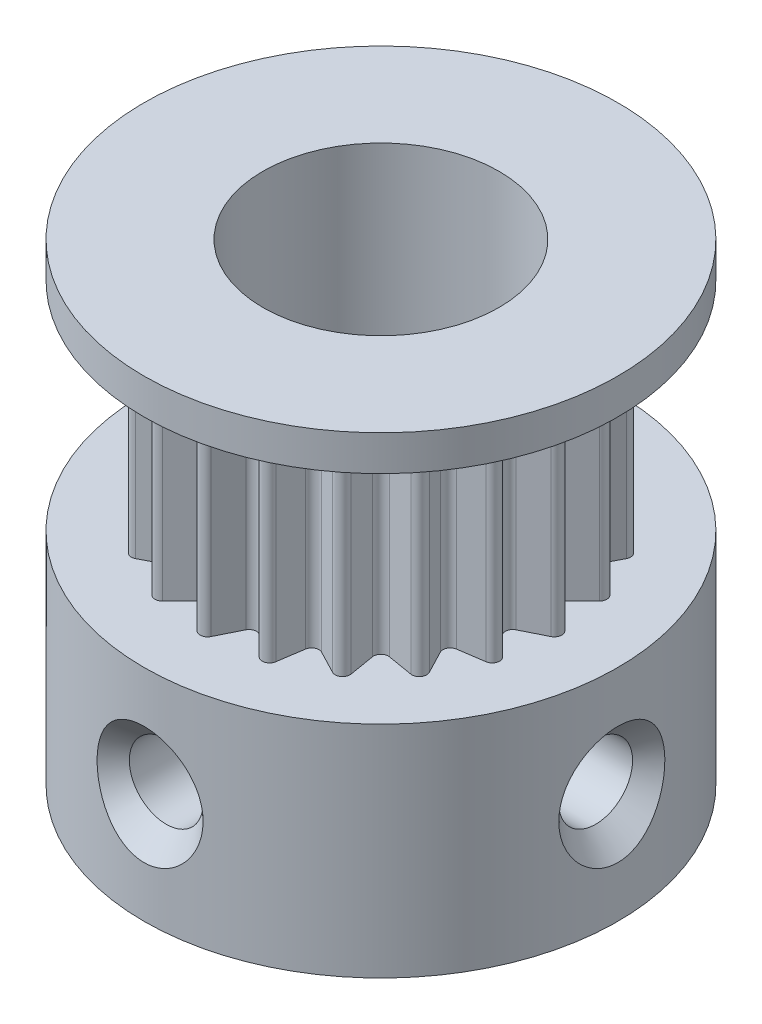
SolidWorks part; units mm, degrees
ref_plane "Front Plane" through (0, 0, 0) normal (0, 0, 1) x (1, 0, 0)
ref_plane "Top Plane" through (0, 0, 0) normal (0, 1, 0) x (1, 0, 0)
ref_plane "Right Plane" through (0, 0, 0) normal (1, 0, 0) x (0, 0, -1)
sketch "Sketch1" plane through (0, 0, 0) normal (0, 1, 0) x (1, 0, 0)
  circle A0 centre (0, 0) radius 8.025
  dimension "D1" = 16.05
extrude "Boss-Extrude1" add sketch "Sketch1" along normal blind 16
sketch "Sketch2" plane through (0, 16, 0) normal (0, 1, 0) x (1, 0, 0)
  line L0 (0.2238, 5.9865) -> (0.6171, 5.1973)
  line L1 (1.0192, 5.1336) -> (1.6371, 5.7627)
  line L2 (0, 0) -> (0, 6.125) construction
  line L3 (0.8408, 5.3088) -> (0.9582, 6.0496) construction
  line L4 (1.8927, 5.8252) -> (0, 0) construction
  line L5 (2.0627, 5.6244) -> (2.1929, 4.7522)
  line L6 (2.5557, 4.5674) -> (3.3378, 4.9747)
  line L7 (3.6998, 4.7117) -> (3.5541, 3.842)
  line L8 (3.842, 3.5541) -> (4.7117, 3.6998)
  line L9 (4.9747, 3.3378) -> (4.5674, 2.5557)
  line L10 (4.7522, 2.1929) -> (5.6244, 2.0627)
  line L11 (5.7627, 1.6371) -> (5.1336, 1.0192)
  line L12 (5.1973, 0.6171) -> (5.9865, 0.2238)
  line L13 (5.9865, -0.2238) -> (5.1973, -0.6171)
  line L14 (5.1336, -1.0192) -> (5.7627, -1.6371)
  line L15 (5.6244, -2.0627) -> (4.7522, -2.1929)
  line L16 (4.5674, -2.5557) -> (4.9747, -3.3378)
  line L17 (4.7117, -3.6998) -> (3.842, -3.5541)
  line L18 (3.5541, -3.842) -> (3.6998, -4.7117)
  line L19 (3.3378, -4.9747) -> (2.5557, -4.5674)
  line L20 (2.1929, -4.7522) -> (2.0627, -5.6244)
  line L21 (1.6371, -5.7627) -> (1.0192, -5.1336)
  line L22 (0.6171, -5.1973) -> (0.2238, -5.9865)
  line L23 (-0.2238, -5.9865) -> (-0.6171, -5.1973)
  line L24 (-1.0192, -5.1336) -> (-1.6371, -5.7627)
  line L25 (-2.0627, -5.6244) -> (-2.1929, -4.7522)
  line L26 (-2.5557, -4.5674) -> (-3.3378, -4.9747)
  line L27 (-3.6998, -4.7117) -> (-3.5541, -3.842)
  line L28 (-3.842, -3.5541) -> (-4.7117, -3.6998)
  line L29 (-4.9747, -3.3378) -> (-4.5674, -2.5557)
  line L30 (-4.7522, -2.1929) -> (-5.6244, -2.0627)
  line L31 (-5.7627, -1.6371) -> (-5.1336, -1.0192)
  line L32 (-5.1973, -0.6171) -> (-5.9865, -0.2238)
  line L33 (-5.9865, 0.2238) -> (-5.1973, 0.6171)
  line L34 (-5.1336, 1.0192) -> (-5.7627, 1.6371)
  line L35 (-5.6244, 2.0627) -> (-4.7522, 2.1929)
  line L36 (-4.5674, 2.5557) -> (-4.9747, 3.3378)
  line L37 (-4.7117, 3.6998) -> (-3.842, 3.5541)
  line L38 (-3.5541, 3.842) -> (-3.6998, 4.7117)
  line L39 (-3.3378, 4.9747) -> (-2.5557, 4.5674)
  line L40 (-2.1929, 4.7522) -> (-2.0627, 5.6244)
  line L41 (-1.6371, 5.7627) -> (-1.0192, 5.1336)
  line L42 (-0.6171, 5.1973) -> (-0.2238, 5.9865)
  line L43 (0, 0) -> (1.0192, 5.1336) construction
  line L44 (0, 0) -> (2.5557, 4.5674) construction
  circle A0 centre (0, 0) radius 6.125 construction
  arc A1 (0.2238, 5.9865) -> (0, 6.125) centre (0, 5.875) ccw
  arc A3 (0.6171, 5.1973) -> (1.0192, 5.1336) centre (0.8408, 5.3088) ccw
  arc A4 (1.6371, 5.7627) -> (1.8927, 5.8252) centre (1.8155, 5.5875) cw
  arc A5 (2.0627, 5.6244) -> (1.8927, 5.8252) centre (1.8155, 5.5875) ccw
  arc A6 (2.1929, 4.7522) -> (2.5557, 4.5674) centre (2.4402, 4.7892) ccw
  arc A7 (3.3378, 4.9747) -> (3.6002, 4.9552) centre (3.4532, 4.753) cw
  arc A8 (3.6998, 4.7117) -> (3.6002, 4.9552) centre (3.4532, 4.753) ccw
  arc A9 (3.5541, 3.842) -> (3.842, 3.5541) centre (3.8007, 3.8007) ccw
  arc A10 (4.7117, 3.6998) -> (4.9552, 3.6002) centre (4.753, 3.4532) cw
  arc A11 (4.9747, 3.3378) -> (4.9552, 3.6002) centre (4.753, 3.4532) ccw
  arc A12 (4.5674, 2.5557) -> (4.7522, 2.1929) centre (4.7892, 2.4402) ccw
  arc A13 (5.6244, 2.0627) -> (5.8252, 1.8927) centre (5.5875, 1.8155) cw
  arc A14 (5.7627, 1.6371) -> (5.8252, 1.8927) centre (5.5875, 1.8155) ccw
  arc A15 (5.1336, 1.0192) -> (5.1973, 0.6171) centre (5.3088, 0.8408) ccw
  arc A16 (5.9865, 0.2238) -> (6.125, 0) centre (5.875, 0) cw
  arc A17 (5.9865, -0.2238) -> (6.125, 0) centre (5.875, 0) ccw
  arc A18 (5.1973, -0.6171) -> (5.1336, -1.0192) centre (5.3088, -0.8408) ccw
  arc A19 (5.7627, -1.6371) -> (5.8252, -1.8927) centre (5.5875, -1.8155) cw
  arc A20 (5.6244, -2.0627) -> (5.8252, -1.8927) centre (5.5875, -1.8155) ccw
  arc A21 (4.7522, -2.1929) -> (4.5674, -2.5557) centre (4.7892, -2.4402) ccw
  arc A22 (4.9747, -3.3378) -> (4.9552, -3.6002) centre (4.753, -3.4532) cw
  arc A23 (4.7117, -3.6998) -> (4.9552, -3.6002) centre (4.753, -3.4532) ccw
  arc A24 (3.842, -3.5541) -> (3.5541, -3.842) centre (3.8007, -3.8007) ccw
  arc A25 (3.6998, -4.7117) -> (3.6002, -4.9552) centre (3.4532, -4.753) cw
  arc A26 (3.3378, -4.9747) -> (3.6002, -4.9552) centre (3.4532, -4.753) ccw
  arc A27 (2.5557, -4.5674) -> (2.1929, -4.7522) centre (2.4402, -4.7892) ccw
  arc A28 (2.0627, -5.6244) -> (1.8927, -5.8252) centre (1.8155, -5.5875) cw
  arc A29 (1.6371, -5.7627) -> (1.8927, -5.8252) centre (1.8155, -5.5875) ccw
  arc A30 (1.0192, -5.1336) -> (0.6171, -5.1973) centre (0.8408, -5.3088) ccw
  arc A31 (0.2238, -5.9865) -> (0, -6.125) centre (0, -5.875) cw
  arc A32 (-0.2238, -5.9865) -> (0, -6.125) centre (0, -5.875) ccw
  arc A33 (-0.6171, -5.1973) -> (-1.0192, -5.1336) centre (-0.8408, -5.3088) ccw
  arc A34 (-1.6371, -5.7627) -> (-1.8927, -5.8252) centre (-1.8155, -5.5875) cw
  arc A35 (-2.0627, -5.6244) -> (-1.8927, -5.8252) centre (-1.8155, -5.5875) ccw
  arc A36 (-2.1929, -4.7522) -> (-2.5557, -4.5674) centre (-2.4402, -4.7892) ccw
  arc A37 (-3.3378, -4.9747) -> (-3.6002, -4.9552) centre (-3.4532, -4.753) cw
  arc A38 (-3.6998, -4.7117) -> (-3.6002, -4.9552) centre (-3.4532, -4.753) ccw
  arc A39 (-3.5541, -3.842) -> (-3.842, -3.5541) centre (-3.8007, -3.8007) ccw
  arc A40 (-4.7117, -3.6998) -> (-4.9552, -3.6002) centre (-4.753, -3.4532) cw
  arc A41 (-4.9747, -3.3378) -> (-4.9552, -3.6002) centre (-4.753, -3.4532) ccw
  arc A42 (-4.5674, -2.5557) -> (-4.7522, -2.1929) centre (-4.7892, -2.4402) ccw
  arc A43 (-5.6244, -2.0627) -> (-5.8252, -1.8927) centre (-5.5875, -1.8155) cw
  arc A44 (-5.7627, -1.6371) -> (-5.8252, -1.8927) centre (-5.5875, -1.8155) ccw
  arc A45 (-5.1336, -1.0192) -> (-5.1973, -0.6171) centre (-5.3088, -0.8408) ccw
  arc A46 (-5.9865, -0.2238) -> (-6.125, 0) centre (-5.875, 0) cw
  arc A47 (-5.9865, 0.2238) -> (-6.125, 0) centre (-5.875, 0) ccw
  arc A48 (-5.1973, 0.6171) -> (-5.1336, 1.0192) centre (-5.3088, 0.8408) ccw
  arc A49 (-5.7627, 1.6371) -> (-5.8252, 1.8927) centre (-5.5875, 1.8155) cw
  arc A50 (-5.6244, 2.0627) -> (-5.8252, 1.8927) centre (-5.5875, 1.8155) ccw
  arc A51 (-4.7522, 2.1929) -> (-4.5674, 2.5557) centre (-4.7892, 2.4402) ccw
  arc A52 (-4.9747, 3.3378) -> (-4.9552, 3.6002) centre (-4.753, 3.4532) cw
  arc A53 (-4.7117, 3.6998) -> (-4.9552, 3.6002) centre (-4.753, 3.4532) ccw
  arc A54 (-3.842, 3.5541) -> (-3.5541, 3.842) centre (-3.8007, 3.8007) ccw
  arc A55 (-3.6998, 4.7117) -> (-3.6002, 4.9552) centre (-3.4532, 4.753) cw
  arc A56 (-3.3378, 4.9747) -> (-3.6002, 4.9552) centre (-3.4532, 4.753) ccw
  arc A57 (-2.5557, 4.5674) -> (-2.1929, 4.7522) centre (-2.4402, 4.7892) ccw
  arc A58 (-2.0627, 5.6244) -> (-1.8927, 5.8252) centre (-1.8155, 5.5875) cw
  arc A59 (-1.6371, 5.7627) -> (-1.8927, 5.8252) centre (-1.8155, 5.5875) ccw
  arc A60 (-1.0192, 5.1336) -> (-0.6171, 5.1973) centre (-0.8408, 5.3088) ccw
  arc A61 (-0.2238, 5.9865) -> (0, 6.125) centre (0, 5.875) cw
  circle A62 centre (0, 0) radius 8.025 construction
  circle A63 centre (0, 0) radius 8.025
  circle M4 centre (0, 0) radius 8.025
  dimension "D1" = 12.25
  dimension "D2" = 0.5
  dimension "D3" = 1
  dimension "D5" = 0.25
  dimension "D4" = 18
  dimension "D7" = 18
  dimension "D6" = 20
extrude "Cut-Extrude1" cut sketch "Sketch2" against normal blind 7.35 from offset 1.2 contours L42 A61 A1 L0 A3 L1 A4 A5 L5 A6 L6 A7 A8 L7 A9 L8 A10 A11 L9 A12 L10 A13 A14 L11 A15 L12 A16 A17 L13 A18 L14 A19 A20 L15 A21 L16 A22 A23 L17 A24 L18 A25 A26 L19 A27 L20 A28 A29 L21 M4 region at (-7.798, 16, 0) offset against normal yes
sketch "Sketch3" plane through (0, 16, 0) normal (0, 1, 0) x (1, 0, 0)
  circle A0 centre (0, 0) radius 4
  dimension "D1" = 8
extrude "Cut-Extrude2" cut sketch "Sketch3" against normal through all
hole_wizard "M3x0.5 Tapped Hole1" positions "3DSketch2" profile "Sketch4" tap size "M3x0.5" standard "ANSI Metric" end condition up to next
sketch3d "3DSketch2"
  line L0 (0, 0, 0) -> (0, 7.45, 0) construction
  line L1 (0, 7.45, 0) -> (0, 0, 0) construction
  line L2 (0, 3.725, 0) -> (0, 3.725, 8.025) construction
  point P9 (0, 3.725, 8.025)
sketch "Sketch4" plane through (0, 3.725, 8.025) normal (1, 0, 0) x (0, -1, 0)
  line L0 (0, 0) -> (0, 4.025)
  line L1 (0, 4.025) -> (1.25, 4.025)
  line L2 (1.25, 4.025) -> (1.25, 0.75)
  line L3 (1.25, 0.75) -> (2, 0)
  line L5 (2, 0) -> (0, 0)
  line L6 (-1.25, 0.75) -> (-2, 0) construction
  line L11 (0, -6.35) -> (0, 107.95) construction
  dimension "Thru Tap Drill Dia." = 2.5
  dimension "Thru Tap Drill Depth" = 4.025
  dimension "Near C'Sink Dia." = 4
  dimension "Near C'Sink Angle" = 90
cosmetic thread "Hole Thread1" parameters "D2"=3
pattern_circular "CirPattern1" count 2 over 90 about axis through (0, 16, 0) along (0, -1, 0) of "M3x0.5 Tapped Hole1" reverse direction yes
cosmetic thread "Hole Thread2" parameters "D2"=3
